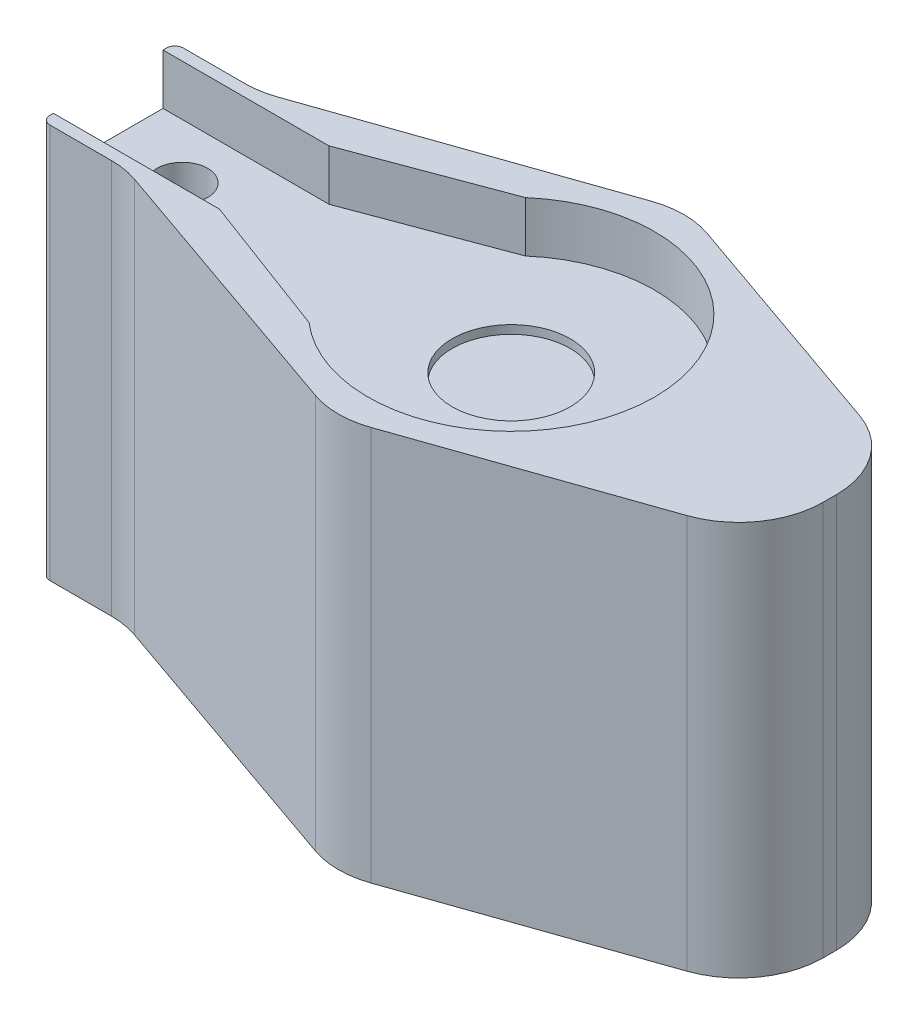
SolidWorks part; units mm, degrees
note: The reader was unsure of these and kept them because the rebuilt part matched: shared geometry of "Sketch3<3>".
ref_plane "Front Plane" through (0, 0, 0) normal (0, 0, 1) x (1, 0, 0)
ref_plane "Top Plane" through (0, 0, 0) normal (0, 1, 0) x (1, 0, 0)
ref_plane "Right Plane" through (0, 0, 0) normal (1, 0, 0) x (0, 0, -1)
sketch "Sketch1" plane through (0, 0, 0) normal (0, 1, 0) x (1, 0, 0)
  line L16 (-2.4, -1.7052) -> (16.5, -8.2916)
  line L22 (0, 0) -> (16.5, -5.75)
  line L23 (16.5, -5.75) -> (33, 0)
  line L24 (33, 0) -> (33, 4.5)
  line L25 (33, 4.5) -> (16.5, 10.25)
  line L26 (16.5, 10.25) -> (0, 4.5)
  line L27 (0, 4.5) -> (0, 0)
  line L28 (16.5, -5.75) -> (16.5, 10.25) construction
  line L29 (33, 2.25) -> (0, 2.25) construction
  line L30 (16.5, -8.2916) -> (35.4, -1.7052)
  line L31 (35.4, -1.7052) -> (35.4, 6.2052)
  line L32 (35.4, 6.2052) -> (16.5, 12.7916)
  line L33 (16.5, 12.7916) -> (-2.4, 6.2052)
  line L34 (-2.4, 6.2052) -> (-2.4, -1.7052)
  line L35 (0, 2.25) -> (-2.4, 2.25) construction
  line L36 (33, 2.25) -> (35.4, 2.25) construction
  line L37 (8.25, -2.875) -> (7.4602, -5.1413) construction
  line L38 (24.75, -2.875) -> (25.5398, -5.1413) construction
  line L39 (8.25, 7.375) -> (7.4602, 9.6413) construction
  line L40 (24.75, 7.375) -> (25.5398, 9.6413) construction
  dimension "D1" = 2.4
  dimension "D6" = 4.5
  dimension "D7" = 16
  dimension "D8" = 33
extrude "Boss-Extrude1" add sketch "Sketch1" against normal blind 15
fillet "Fillet2" radius 2 1 edges at (0, -7.5, -4.5)
fillet "Fillet3" radius 2 1 edges at (16.5, -7.5, -10.25)
fillet "Fillet4" radius 2 1 edges at (33, -7.5, -4.5)
fillet "Fillet5" radius 2 1 edges at (0, -7.5, 0)
fillet "Fillet6" radius 2 1 edges at (16.5, -7.5, 5.75)
fillet "Fillet7" radius 2 1 edges at (33, -7.5, 0)
sketch "Sketch2" plane through (0, 0, 0) normal (0, 1, 0) x (1, 0, 0)
  line L0 (16.5, -8.2916) -> (-2.4, -1.7052)
  line L1 (-2.4, -1.7052) -> (-2.4, 6.2052)
  line L2 (-2.4, 6.2052) -> (16.5, 12.7916)
  line L3 (16.5, 12.7916) -> (35.4, 6.2052)
  line L4 (35.4, 6.2052) -> (35.4, -1.7052)
  line L5 (35.4, -1.7052) -> (16.5, -8.2916)
extrude "Boss-Extrude2" add sketch "Sketch2" along normal blind 8.4
sketch "Sketch3" plane through (0, 8.4, 0) normal (0, 1, 0) x (1, 0, 0)
  line L0 (16.5, -8.2916) -> (16.5, 12.7916) construction
  line L1 (16.5, -6.25) -> (2.4488, -1)
  line L2 (-2.4, 6.2052) -> (-2.4, -1.7052) construction
  line L3 (-2.4, 2.25) -> (35.4, 2.25) construction
  line L4 (35.4, -1.7052) -> (35.4, 6.2052) construction
  line L5 (25, 2.25) -> (-10, 2.25)
  line L6 (25, 2.25) -> (25, -1)
  line L7 (25, -1) -> (-10, -1)
  line L8 (-10, 2.25) -> (-10, -1)
  line L9 (25, 2.25) -> (-10, 2.25)
  line L10 (25, 2.25) -> (25, 5.5)
  line L11 (25, 5.5) -> (-10, 5.5)
  line L12 (-10, 2.25) -> (-10, 5.5)
  line L13 (2.4488, -1) -> (2.4488, 5.5)
  line L14 (2.4488, 5.5) -> (16.5, 10.75)
  line L15 (16.5, -6.25) -> (16.5, 10.75)
  circle A0 centre (16.5, 2.25) radius 8.5
  circle A1 centre (-3, 2.25) radius 1.5
  line M11 (-2.4, 6.2052) -> (-2.4, -1.7052)
  dimension "D2" = 17
  dimension "D3" = 3
  dimension "D1" = 3.25
  dimension "D4" = 35
  dimension "D5" = 19.5
  dimension "D6" = 15
sketch "Sketch4" plane through (-2.4, 0, 0) normal (-1, 0, 0) x (0, 0, 1)
  line L1 (-6.2052, -15) -> (1.7052, -15)
  line L2 (-6.2052, -15) -> (-6.2052, 8.4)
  line L3 (-6.2052, 8.4) -> (1.7052, 8.4)
  line L4 (1.7052, -15) -> (1.7052, 8.4)
extrude "Boss-Extrude3" add sketch "Sketch4" along normal blind 5
extrude "Cut-Extrude1" cut sketch "Sketch3" against normal blind 6 contours L5 A1 M11 | A1 L5 M11 | L5 A1 M11 | A1 L5 M11
extrude "Cut-Extrude2" cut sketch "Sketch3<3>" against normal blind 3 contours L15 A0 L7 | L7 A0 L1 L15 | L1 A0 | L7 A0 L5 L15 | L5 A0 L11 L15 | L11 A0 L15 | L14 A0 L11 L15 | L14 A0 | L11 A0 L9 L15 | L9 A0 L7 L15 | A0 L7 L1 | A0 L5 L13 L7 | A0 L11 L13 L5 | A0 L14 L11 | A1 L7 L13 L9 M11 | A1 L9 L13 L11 M11 | A1 L11 L12 L9 M11 | A1 L9 L8 L7 M11
sketch "Sketch3<3>" plane through (0, 8.4, 0) normal (0, 1, 0) x (1, 0, 0) same geometry as "Sketch3"
sketch "Sketch5" plane through (0, 5.4, 0) normal (0, 1, 0) x (1, 0, 0)
  line L0 (-1.5, 2.25) -> (25, 2.25) construction
  line L2 (16.5, -6.25) -> (16.5, 10.75) construction
  circle A0 centre (-3, 2.25) radius 1.5 construction
  circle A1 centre (-3, 2.25) radius 1.5 construction
  arc A2 (10.9263, -4.1675) -> (10.9263, 8.6675) centre (16.5, 2.25) ccw construction
  arc A3 (10.9263, -4.1675) -> (10.9263, 8.6675) centre (16.5, 2.25) ccw construction
  circle A4 centre (16.5, 2.25) radius 3.5
  dimension "D1" = 7
extrude "Cut-Extrude3" cut sketch "Sketch5" against normal blind 0.5
fillet "Fillet8" radius 0.5 1 edges at (-7.4, -3.3, -6.2052)
fillet "Fillet9" radius 0.5 1 edges at (-7.4, -3.3, 1.7052)
fillet "Fillet10" radius 5 1 edges at (-2.4, -3.3, -6.2052)
fillet "Fillet11" radius 5 1 edges at (-2.4, -3.3, 1.7052)
fillet "Fillet12" radius 5 1 edges at (16.5, -3.3, 8.2916)
fillet "Fillet13" radius 5 1 edges at (16.5, -3.3, -12.7916)
fillet "Fillet14" radius 5 1 edges at (35.4, -3.3, -6.2052)
fillet "Fillet15" radius 5 1 edges at (35.4, -3.3, 1.7052)
